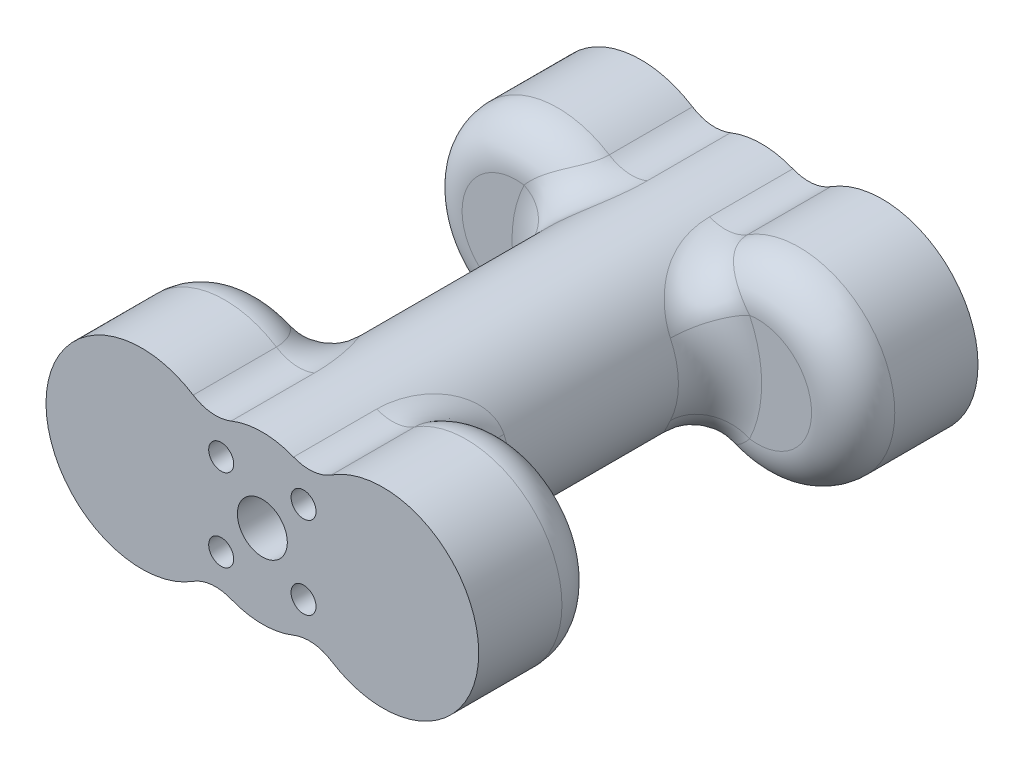
SolidWorks part; units mm, degrees
ref_plane "前视基准面" through (0, 0, 0) normal (0, 0, 1) x (1, 0, 0)
ref_plane "上视基准面" through (0, 0, 0) normal (0, 1, 0) x (1, 0, 0)
ref_plane "右视基准面" through (0, 0, 0) normal (1, 0, 0) x (0, 0, -1)
other "Configuration Table"
sketch "草图1" plane through (0, 0, 0) normal (0, 0, 1) x (1, 0, 0)
  line L0 (0, 0) -> (0, 10) construction
  line L6 (0, 0) -> (0, -10) construction
  circle A0 centre (0, 0) radius 3
  circle A1 centre (0, 0) radius 7 construction
  circle A2 centre (4.9497, 4.9497) radius 1.5
  circle A3 centre (4.9497, -4.9497) radius 1.5
  circle A4 centre (-4.9497, -4.9497) radius 1.5
  circle A5 centre (-4.9497, 4.9497) radius 1.5
  arc A6 (-6.1379, -7.8947) -> (6.1379, -7.8947) centre (0, 0) ccw
  arc A7 (-6.1379, 7.8947) -> (-6.1379, -7.8947) centre (-14.5, 0) ccw
  arc A9 (6.1379, 7.8947) -> (6.1379, -7.8947) centre (14.5, 0) cw
  arc A10 (6.1379, 7.8947) -> (-6.1379, 7.8947) centre (0, 0) ccw
  point P15 (0, 0)
  dimension "D1" = 4
  dimension "D2" = 3
  dimension "D3" = 14
  dimension "D4" = 6
  dimension "D5" = 4.9497
  dimension "D6" = 20
  dimension "D7" = 23
extrude "凸台-拉伸4" add sketch "草图1" along normal blind 15
sketch "草图3" plane through (0, 0, 15) normal (0, 0, 1) x (1, 0, 0)
  circle A0 centre (0, 0) radius 10
  circle A1 centre (0, 0) radius 3
  circle A2 centre (4.9497, -4.9497) radius 1.5
  circle A3 centre (4.9497, 4.9497) radius 1.5
  circle A4 centre (-4.9497, 4.9497) radius 1.5
  circle A5 centre (-4.9497, -4.9497) radius 1.5
extrude "凸台-拉伸5" add sketch "草图3" along normal blind 15
fillet "圆角5" radius 5 8 edges at (26, 0, 15) (-26, 0, 15) (6.1379, -7.8947, 7.5) (-6.1379, -7.8947, 7.5) (10, 0, 15) (-10, 0, 15) (-6.1379, 7.8947, 7.5) (6.1379, 7.8947, 7.5)
mirror "镜向3" about plane through (0, 0, 30) normal (0, 0, 1) of bodies 110
